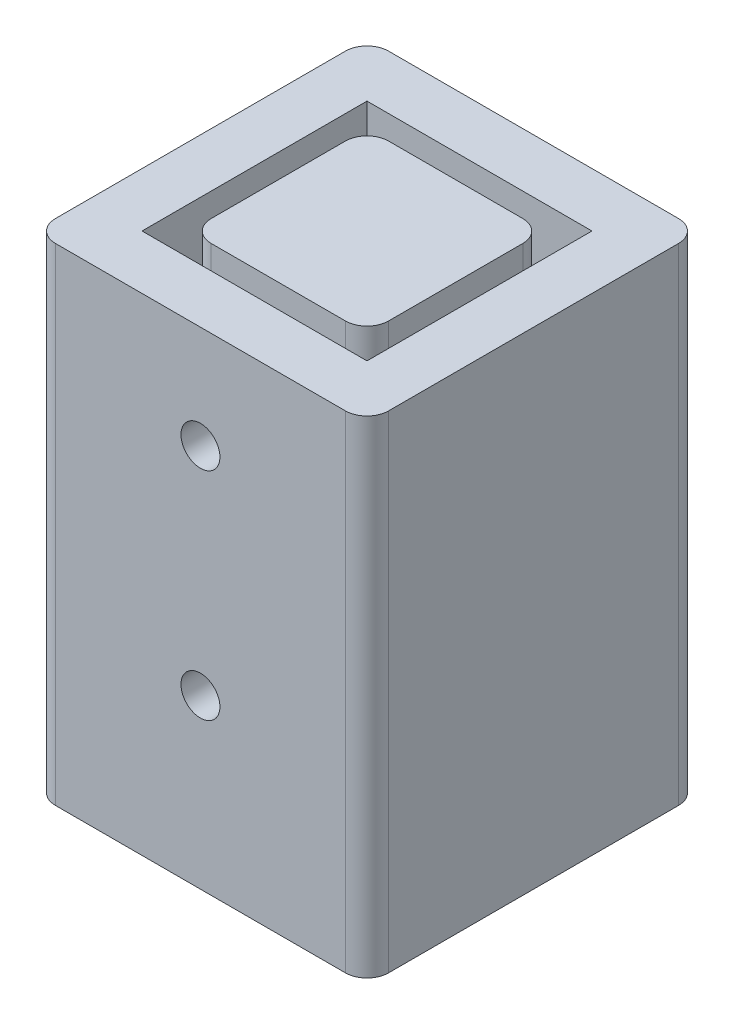
SolidWorks part; units mm, degrees
ref_plane "Front Plane" through (0, 0, 0) normal (0, 0, 1) x (1, 0, 0)
ref_plane "Top Plane" through (0, 0, 0) normal (0, 1, 0) x (1, 0, 0)
ref_plane "Right Plane" through (0, 0, 0) normal (1, 0, 0) x (0, 0, -1)
sketch "Sketch1" plane through (0, 0, 0) normal (0, 1, 0) x (1, 0, 0)
  line L0 (-19.558, -19.558) -> (19.558, -19.558)
  line L1 (-13.208, -13.208) -> (13.208, -13.208)
  line L2 (-13.208, -13.208) -> (-13.208, 13.208)
  line L3 (-13.208, 13.208) -> (13.208, 13.208)
  line L4 (13.208, -13.208) -> (13.208, 13.208)
  line L5 (-13.208, -13.208) -> (13.208, 13.208) construction
  line L6 (-13.208, 13.208) -> (13.208, -13.208) construction
  line L7 (19.558, -19.558) -> (19.558, 19.558)
  line L8 (-19.558, 19.558) -> (19.558, 19.558)
  line L9 (-19.558, -19.558) -> (-19.558, 19.558)
  line L11 (10.414, 10.414) -> (-10.414, 10.414)
  line L12 (10.414, 10.414) -> (10.414, -10.414)
  line L13 (10.414, -10.414) -> (-10.414, -10.414)
  line L14 (-10.414, 10.414) -> (-10.414, -10.414)
  line L15 (10.414, 10.414) -> (-10.414, -10.414) construction
  line L16 (10.414, -10.414) -> (-10.414, 10.414) construction
  point P0 (0, 0)
  point P10 (0, 0)
  dimension "D1" = 26.416
  dimension "D2" = 6.35
  dimension "D3" = 20.828
  dimension "D4" = 20.828
extrude "Boss-Extrude1" add sketch "Sketch1" along normal blind 50.8 contours L11 L14 L13 L12 | L9 L0 L7 L8 L4 L1 L2 L3 region at (-19.0048, 0, 0) region at (0, 0, 0)
sketch "Sketch2" plane through (0, 0, 19.558) normal (0, 0, 1) x (1, 0, 0)
  line L1 (0, 50.8) -> (0, 0) construction
  circle A4 centre (0, 13.335) radius 2.286
  circle A5 centre (0, 38.735) radius 2.286
  dimension "D1" = 13.335
  dimension "D2" = 25.4
  dimension "D3" = 4.572
extrude "Cut-Extrude1" cut sketch "Sketch2" against normal through all
extrude "Boss-Extrude2" add sketch "Sketch1<2>" against normal blind 6.35 contours L9 L0 L7 L8 L4 L1 L2 L3 | L1 L4 L3 L2 L14 L11 L12 L13 | L11 L14 L13 L12 region at (-19.0048, 0, 0) region at (-12.8344, 0, 0) region at (0, 0, 0)
sketch "Sketch1<2>" plane through (0, 0, 0) normal (0, 1, 0) x (1, 0, 0) same geometry as "Sketch1"
fillet "Fillet1" radius 2.54 8 edges at (19.558, 22.225, -19.558) (-19.558, 22.225, -19.558) (19.558, 22.225, 19.558) (-19.558, 22.225, 19.558) (10.414, 25.4, -10.414) (-10.414, 25.4, 10.414) (10.414, 25.4, 10.414) (-10.414, 25.4, -10.414)
